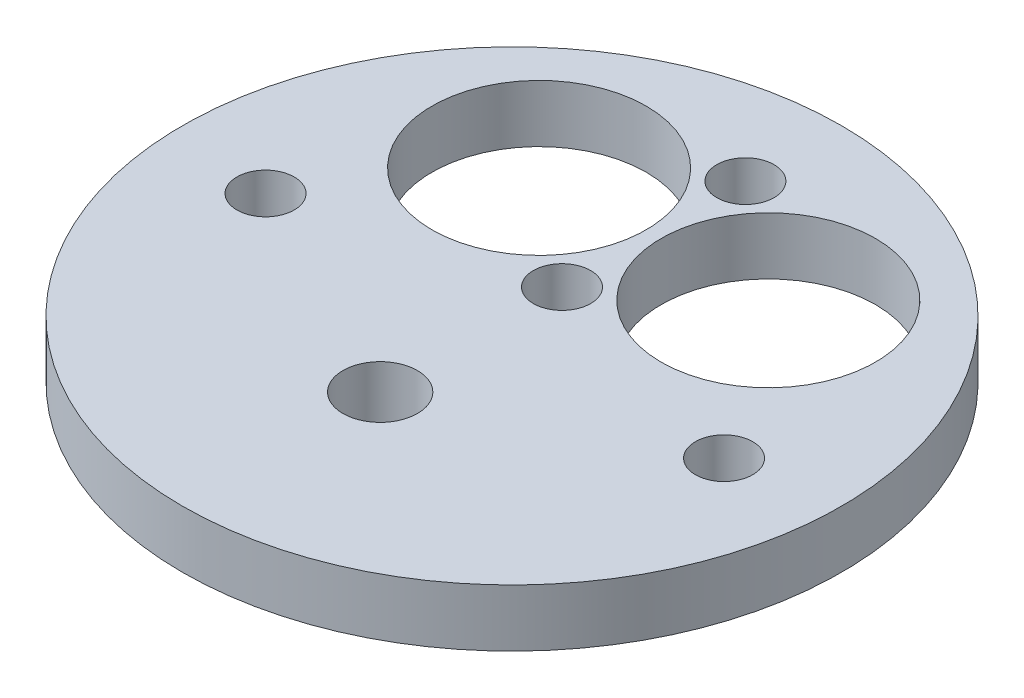
SolidWorks part; units mm, degrees
ref_plane "Front Plane" through (0, 0, 0) normal (0, 0, 1) x (1, 0, 0)
ref_plane "Top Plane" through (0, 0, 0) normal (0, 1, 0) x (1, 0, 0)
ref_plane "Right Plane" through (0, 0, 0) normal (1, 0, 0) x (0, 0, -1)
ref_axis "Axis1" through (0, 55, 0) along (0, -1, 0)
sketch "Sketch1" plane through (0, 0, 0) normal (0, 0, 1) x (1, 0, 0)
  line L0 (0, 0) -> (36.5125, 0)
  line L3 (36.5125, 0) -> (36.5125, 6.35)
  line L4 (36.5125, 6.35) -> (0, 6.35)
  line L5 (0, 55) -> (0, -55) construction
  line L6 (0, 6.35) -> (0, 0)
  line L7 (0, 0) -> (0, 21.2966) construction
  dimension "D1" = 73.025
  dimension "D2" = 6.35
revolve "Revolve1" add sketch "Sketch1" angle 360 about L7
sketch "Sketch2" plane through (0, 6.35, 0) normal (0, 1, 0) x (1, 0, 0)
  line L0 (-12.7, 15.6993) -> (12.7, 15.6993) construction
  line L1 (0, 25.8593) -> (0, 5.5393) construction
  line L2 (-12.7, 15.6993) -> (12.7, 15.6993) construction
  line L3 (-12.7, 29.6693) -> (12.7, 29.6693) construction
  line L4 (-12.7, 1.7293) -> (12.7, 1.7293) construction
  circle A0 centre (-12.7, 15.6993) radius 11.8745
  circle A1 centre (0, 0) radius 36.5125
  circle A3 centre (12.7, 15.6993) radius 11.8745
  circle A4 centre (0, 25.8593) radius 3.175
  circle A5 centre (0, 5.5393) radius 3.175
  arc A6 (-12.7, 29.6693) -> (-12.7, 1.7293) centre (-12.7, 15.6993) ccw construction
  arc A7 (12.7, 1.7293) -> (12.7, 29.6693) centre (12.7, 15.6993) ccw construction
  circle A8 centre (0, -14.605) radius 4.1275
  circle A9 centre (0, 0) radius 34.163 construction
  circle A11 centre (0, 0) radius 36.5125 construction
  point P11 (0, 15.6993)
  point P12 (0, 15.6993)
  point P15 (0, 15.6993)
  dimension "D2" = 23.749
  dimension "D3" = 23.749
  dimension "D5" = 6.35
  dimension "D6" = 6.35
  dimension "D11" = 8.255
  dimension "D4" = 25.4
  dimension "D7" = 20.32
  dimension "D8" = 25.4
  dimension "D9" = 27.94
  dimension "D10" = 14.605
  dimension "D1" = 0
extrude "Cut-Extrude1" cut sketch "Sketch2" against normal through all both and the other way through all
sketch "Sketch3" plane through (0, 6.35, 0) normal (0, 1, 0) x (1, 0, 0)
  circle A0 centre (-25.4, -1.905) radius 3.175
  circle A1 centre (25.4, -1.905) radius 3.175
  circle A2 centre (0, -14.605) radius 4.1275 construction
  dimension "D1" = 6.35
  dimension "D2" = 6.35
  dimension "D3" = 50.8
  dimension "D4" = 12.7
  dimension "D5" = 1.905
extrude "Cut-Extrude2" cut sketch "Sketch3" against normal through all both
ref_plane "Plane1" through (0, 3.175, 0) normal (0, 1, 0) x (-1, 0, 0)
equation "\"D3@Sketch2\"=\"D2@Sketch2\""
equation "\"D6@Sketch2\"=\"D5@Sketch2\""
